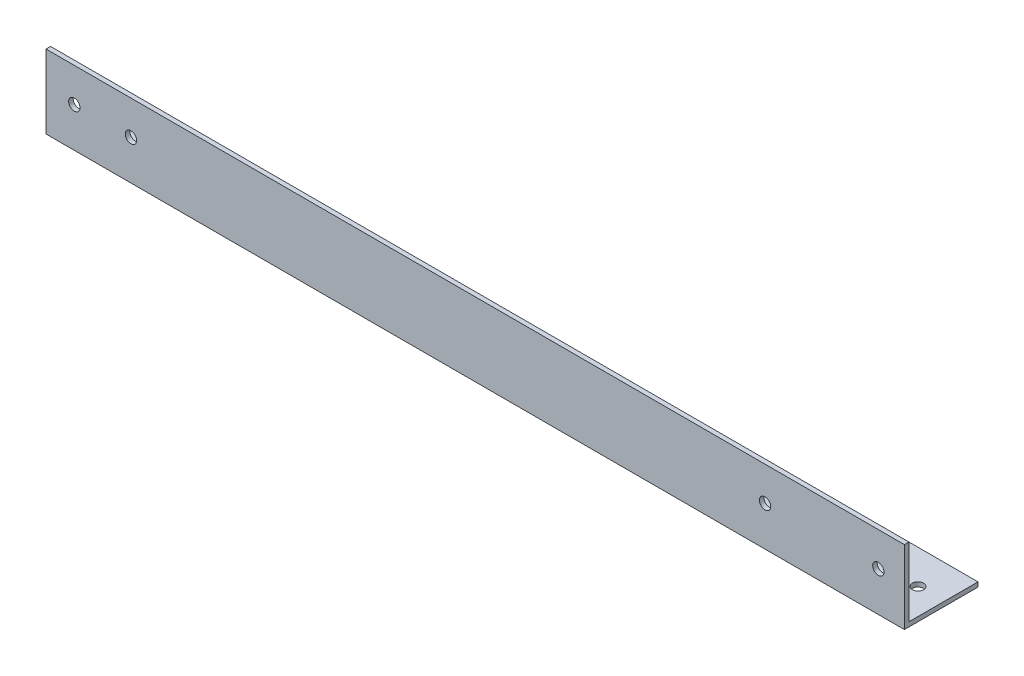
SolidWorks part; units mm, degrees
ref_plane "Спереди" through (0, 0, 0) normal (0, 0, 1) x (1, 0, 0)
ref_plane "Сверху" through (0, 0, 0) normal (0, 1, 0) x (1, 0, 0)
ref_plane "Справа" through (0, 0, 0) normal (1, 0, 0) x (0, 0, -1)
sketch "Эскиз1" plane through (0, 0, 0) normal (1, 0, 0) x (0, 0, -1)
  line L0 (0, 0) -> (0, 65)
  line L1 (0, 0) -> (65, 0)
extrude "Вытянуть-Тонкостенный1" add sketch "Эскиз1" along normal blind 758 thin thin type one direction reverse wall 4
sketch "Эскиз2" plane through (0, 0, 0) normal (0, 0, 1) x (1, 0, 0)
  circle A0 centre (25, 35) radius 5
  circle A1 centre (75, 35) radius 5
  circle A2 centre (735, 35) radius 5
  circle A6 centre (635, 35) radius 5
  dimension "D2" = 2
  dimension "D1" = 2
extrude "Вырез-Вытянуть1" cut sketch "Эскиз2" against normal blind 10
sketch "Эскиз3" plane through (0, 0, 0) normal (0, -1, 0) x (1, 0, 0)
  circle A0 centre (25, -35) radius 5
  circle A1 centre (75, -35) radius 5
  circle A2 centre (735, -35) radius 5
  circle A6 centre (635, -35) radius 5
  dimension "D1" = 2
  dimension "D2" = 2
extrude "Вырез-Вытянуть2" cut sketch "Эскиз3" against normal blind 10
